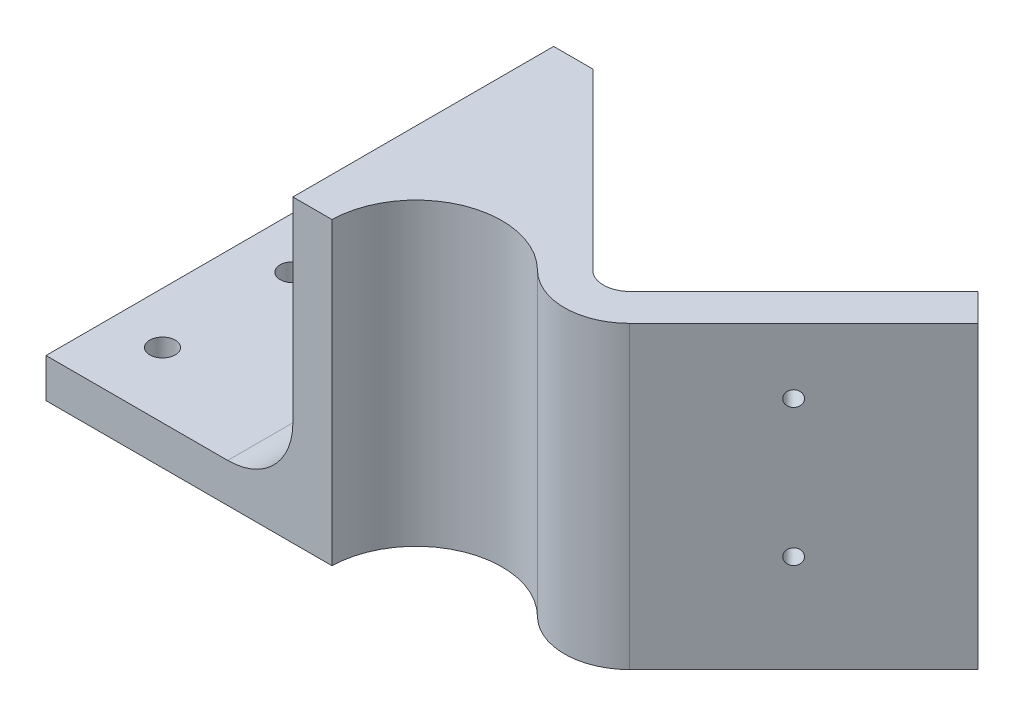
SolidWorks part; units mm, degrees
ref_plane "Front Plane" through (0, 0, 0) normal (0, 0, 1) x (1, 0, 0)
ref_plane "Top Plane" through (0, 0, 0) normal (0, 1, 0) x (1, 0, 0)
ref_plane "Right Plane" through (0, 0, 0) normal (1, 0, 0) x (0, 0, -1)
sketch "Sketch1" plane through (0, 0, 0) normal (0, 1, 0) x (1, 0, 0)
  line L0 (3.5921, -3.5921) -> (37.5275, 30.3433)
  line L1 (-3.5921, -3.5921) -> (-37.5275, 30.3433)
  line L2 (37.5275, 30.3433) -> (42.9156, 24.9551)
  line L3 (42.9156, 24.9551) -> (8.9803, -8.9803)
  line L4 (-45.1475, 30.3433) -> (-93.2475, 30.3433)
  line L7 (-37.5275, -20.4567) -> (-45.1475, -20.4567)
  line L8 (-45.1475, -20.4567) -> (-45.1475, 30.3433)
  line L9 (-45.1475, 30.3433) -> (-37.5275, 30.3433)
  line L11 (-93.2475, 30.3433) -> (-93.2475, -20.4567)
  line L12 (-93.2475, -20.4567) -> (-45.1475, -20.4567)
  line L13 (20.5598, 13.3756) -> (-20.5598, 13.3756)
  arc A1 (8.9803, -8.9803) -> (-8.9803, -8.9803) centre (0, 0) cw
  arc A2 (-8.9803, -8.9803) -> (-37.5275, -20.4567) centre (-20.8064, -20.8064) ccw
  arc A3 (-3.5921, -3.5921) -> (3.5921, -3.5921) centre (0, 0) ccw
  circle A4 centre (-83.2475, 17.6433) radius 2.5
  circle A5 centre (-83.2475, -7.7567) radius 2.5
  point P17 (-24.0768, -24.0768)
  point P21 (0, 0)
  point P22 (-37.5275, -20.8049)
  point P23 (-37.5275, -20.4602)
  point P25 (-37.5275, -19.1505)
  point P26 (-37.5275, -20.338)
  point P27 (0, 0)
  point P28 (0, 0)
  dimension "D4" = 5.08
  dimension "D9" = 5
  dimension "D1" = 7.62
  dimension "D2" = 90
  dimension "D3" = 48.26
  dimension "D5" = 7.62
  dimension "D6" = 50.8
  dimension "D8" = 38.1
  dimension "D10" = 12.7
  dimension "D11" = 12.7
  dimension "D12" = 10
extrude "Boss-Extrude1" add sketch "Sketch1" along normal blind 50.8 contours A3 L1 L9 L8 L7 A2 A1 L3 L2 L0 region at (-16.388, 0, -5.6189)
extrude "Boss-Extrude2" add sketch "Sketch1<3>" against normal blind 7.62 contours L1 A3 L0 | A3 L1 L9 L8 L7 A2 A1 L3 L2 L0 | L11 L12 L8 L4 A5 A4 region at (0, 0, -6.683) region at (-16.388, 0, -5.6189) region at (-68.968, 0, -4.9433)
sketch "Sketch1<3>" plane through (0, 0, 0) normal (0, 1, 0) x (1, 0, 0) same geometry as "Sketch1"
sketch "Sketch2" plane through (-3.5921, 0, 3.5921) normal (0.7071, 0, -0.7071) x (-0.7071, 0, -0.7071)
  line L1 (0, 50.8) -> (47.9919, 50.8) construction
  line L2 (23.9959, -7.62) -> (47.9919, -7.62) construction
  line L3 (47.9919, 50.8) -> (47.9919, -7.62) construction
  circle A0 centre (22.5919, 38.1) radius 1.5
  circle A1 centre (22.5919, 11.43) radius 1.5
  point P4 (24.107, 39.4667)
  point P5 (24.8677, 12.2333)
  point P6 (24.5634, 39.6188)
  point P9 (22.5919, 38.5538)
  point P14 (22.5919, 38.1)
  dimension "D4" = 3
  dimension "D1" = 25.4
  dimension "D2" = 12.7
  dimension "D3" = 19.05
sketch "Sketch3" plane through (3.5921, 0, 3.5921) normal (-0.7071, 0, -0.7071) x (-0.7071, 0, 0.7071)
  line L0 (0, 50.8) -> (-47.9919, 50.8) construction
  line L1 (-23.9959, -7.62) -> (-47.9919, -7.62) construction
  line L2 (-47.9919, 50.8) -> (-47.9919, -7.62) construction
  circle A0 centre (-22.5919, 38.1) radius 1.5
  circle A1 centre (-22.5919, 11.43) radius 1.5
  point P4 (-23.8139, 38.4017)
  dimension "D1" = 3
  dimension "D2" = 12.7
  dimension "D3" = 19.05
  dimension "D4" = 25.4
extrude "Cut-Extrude1" cut sketch "Sketch2" against normal blind 12.7
extrude "Cut-Extrude2" cut sketch "Sketch3" against normal blind 12.7
fillet "Fillet1" radius 12.7 1 edges at (-45.1475, 0, -4.9433)
